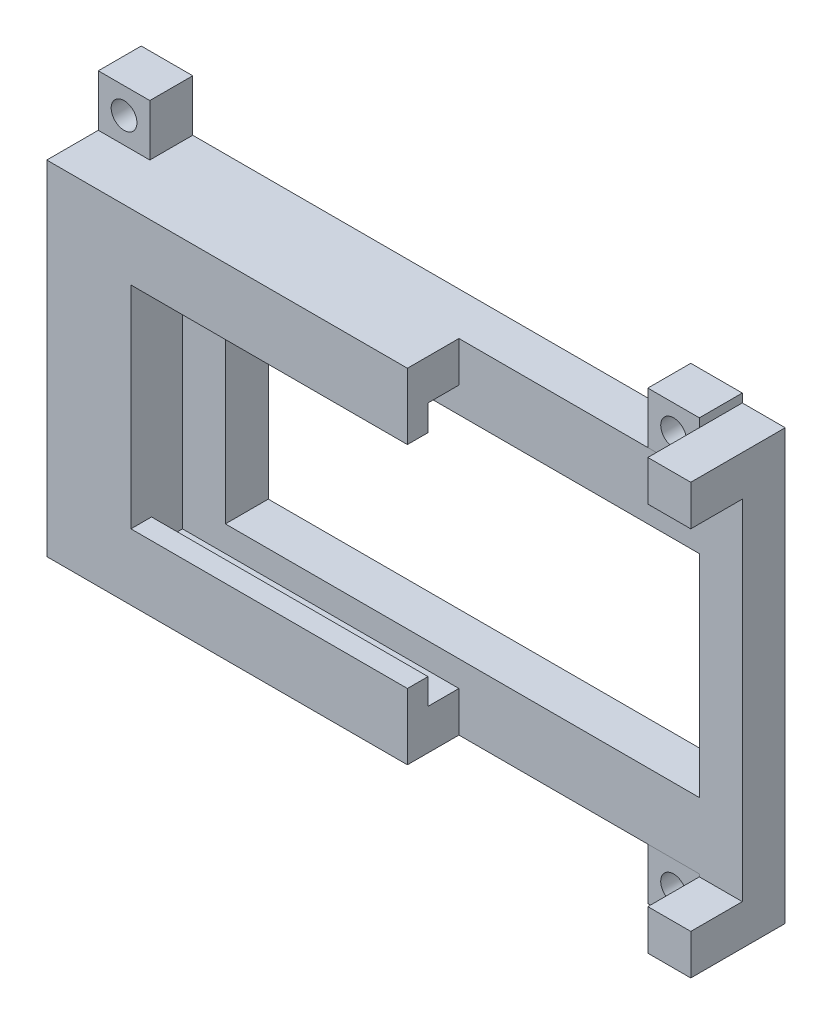
SolidWorks part; units mm, degrees
ref_plane "Front Plane" through (0, 0, 0) normal (1, 0, 0) x (0, 1, 0)
ref_plane "Top Plane" through (0, 0, 0) normal (0, 0, 1) x (0, 1, 0)
ref_plane "Right Plane" through (0, 0, 0) normal (0, 1, 0) x (-1, 0, 0)
sketch "Sketch1" plane through (0, 0, 0) normal (0, 0, 1) x (0, 1, 0)
  line L2 (-20, 5) -> (-20, 75)
  line L3 (-20, 75) -> (20, 75)
  line L4 (20, 5) -> (20, 75)
  line L5 (-25, 0) -> (-25, 5)
  line L6 (-25, 5) -> (-20, 5)
  line L7 (0, 75) -> (0, 0) construction
  line L9 (25, 0) -> (25, 5)
  line L10 (25, 5) -> (20, 5)
  line L11 (-25, 0) -> (25, 0)
  dimension "D1" = 40
  dimension "D2" = 5
  dimension "D3" = 5
  dimension "D4" = 75
extrude "Boss-Extrude1" add sketch "Sketch1" along normal blind 5
sketch "Sketch4" plane through (0, 0, 5) normal (0, 0, 1) x (1, 0, 0)
  line L0 (-75, 20) -> (-75, -20)
  line L1 (-5, 20.3) -> (0, 20.3)
  line L2 (-5, 20.3) -> (-5, 25)
  line L3 (-5, 25) -> (0, 25)
  line L4 (0, 20.3) -> (0, 25)
  line L9 (-75, 20) -> (-33, 20)
  line L11 (-65.2, 15.3) -> (-33, 15.3)
  line L12 (-33, 20) -> (-33, 15.3)
  line L13 (-75, -20) -> (-33, -20)
  line L15 (-65.2, -15.3) -> (-33, -15.3)
  line L16 (-33, -20) -> (-33, -15.3)
  line L17 (-65.2, 15.3) -> (-65.2, -15.3)
  line L18 (-5, 20) -> (-75, 20) construction
  line L19 (-5, 25) -> (-5, 20) construction
  line L20 (0, 0) -> (-65.2, 0) construction
  line L21 (-5, -25) -> (0, -25)
  line L22 (0, -20.3) -> (0, -25)
  line L23 (-5, -20.3) -> (0, -20.3)
  line L24 (-5, -20.3) -> (-5, -25)
  dimension "D1" = 4.7
  dimension "D2" = 32.2
  dimension "D3" = 4.7
  dimension "D4" = 9.8
  dimension "D5" = 0.3
extrude "Boss-Extrude2" add sketch "Sketch4" along normal blind 6
sketch "Sketch5" plane through (-65.2, 0, 0) normal (1, 0, 0) x (0, 1, 0)
  line L0 (0, 11) -> (0, 5) construction
  line L1 (-15.3, 11) -> (-12.3, 11)
  line L2 (-15.3, 11) -> (-15.3, 8.6)
  line L3 (-15.3, 8.6) -> (-12.3, 8.6)
  line L4 (-12.3, 11) -> (-12.3, 8.6)
  line L5 (-15.3, 11) -> (15.3, 11) construction
  line L6 (-15.3, 5) -> (15.3, 5) construction
  line L7 (15.3, 8.6) -> (12.3, 8.6)
  line L8 (12.3, 11) -> (12.3, 8.6)
  line L9 (15.3, 11) -> (12.3, 11)
  line L10 (15.3, 11) -> (15.3, 8.6)
  dimension "D1" = 3
  dimension "D2" = 2.4
extrude "Boss-Extrude3" add sketch "Sketch5" along normal up to surface (32.2 mm away) up to face at (-33, -17.65, 8)
sketch "Sketch6" plane through (0, 0, 0) normal (0, 0, -1) x (1, 0, 0)
  line L0 (-40, 20) -> (-40, -20) construction
  line L1 (-5, 20) -> (-11, 20)
  line L2 (-5, 20) -> (-5, 26)
  line L3 (-5, 26) -> (-11, 26)
  line L4 (-11, 20) -> (-11, 26)
  line L5 (-75, 20) -> (-5, 20) construction
  line L6 (-5, -20) -> (-75, -20) construction
  line L7 (-75, 0) -> (0, 0) construction
  line L8 (-75, -20) -> (-75, 20) construction
  line L9 (-75, 26) -> (-69, 26)
  line L10 (-69, 20) -> (-69, 26)
  line L11 (-75, 20) -> (-69, 20)
  line L12 (-75, 20) -> (-75, 26)
  line L13 (-5, -26) -> (-11, -26)
  line L14 (-11, -20) -> (-11, -26)
  line L15 (-5, -20) -> (-11, -20)
  line L16 (-5, -20) -> (-5, -26)
  line L17 (-75, -20) -> (-75, -26)
  line L18 (-75, -20) -> (-69, -20)
  line L19 (-69, -20) -> (-69, -26)
  line L20 (-75, -26) -> (-69, -26)
  dimension "D1" = 6
extrude "Boss-Extrude4" add sketch "Sketch6" against normal blind 5 separate body
sketch "Sketch7" plane through (0, 0, 5) normal (0, 0, 1) x (1, 0, 0)
  line L0 (-11, -23) -> (-5, -23) construction
  line L1 (-11, -26) -> (-11, -20) construction
  line L2 (-5, -20) -> (-5, -26) construction
  line L3 (0, 0) -> (-65.2, 0) construction
  line L4 (-65.2, -15.3) -> (-65.2, 15.3) construction
  line L5 (-75, -23) -> (-69, -23) construction
  line L6 (-75, -26) -> (-75, -20) construction
  line L7 (-69, -20) -> (-69, -26) construction
  circle A0 centre (-8, -23) radius 1.5
  circle A1 centre (-72, -23) radius 1.5
  circle A2 centre (-8, 23) radius 1.5
  circle A3 centre (-72, 23) radius 1.5
  dimension "D1" = 3
  dimension "D2" = 3
extrude "Cut-Extrude1" cut sketch "Sketch7" against normal through all
sketch "Sketch8" plane through (0, 0, 5) normal (0, 0, 1) x (1, 0, 0)
  line L1 (-60.2, -12.3) -> (-5, -12.3)
  line L2 (-60.2, -12.3) -> (-60.2, 12.3)
  line L3 (-60.2, 12.3) -> (-5, 12.3)
  line L4 (-5, -12.3) -> (-5, 12.3)
  line L6 (-65.2, -15.3) -> (-65.2, 15.3) construction
  line L7 (-33, 12.3) -> (-65.2, 12.3) construction
  line L8 (-33, -12.3) -> (-65.2, -12.3) construction
  line L9 (0, -20.3) -> (0, 20.3) construction
  dimension "D1" = 5
  dimension "D2" = 5
extrude "Cut-Extrude2" cut sketch "Sketch8" against normal through all
